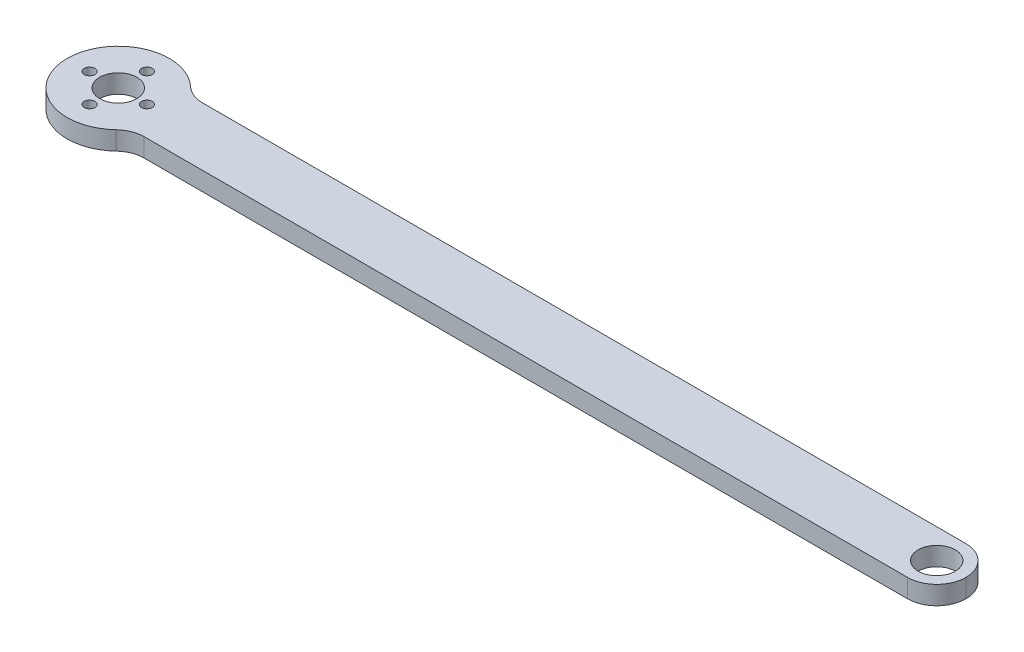
SolidWorks part; units mm, degrees
material "ABS"
ref_plane "Front Plane" through (0, 0, 0) normal (0, 0, 1) x (1, 0, 0)
ref_plane "Top Plane" through (0, 0, 0) normal (0, 1, 0) x (1, 0, 0)
ref_plane "Right Plane" through (0, 0, 0) normal (1, 0, 0) x (0, 0, -1)
sketch "Sketch1" plane through (0, 0, 0) normal (0, 1, 0) x (1, 0, 0)
  line L1 (-150, 10) -> (150, 10)
  line L2 (-150, 10) -> (-150, -10)
  line L3 (-150, -10) -> (150, -10)
  line L4 (150, 10) -> (150, -10)
  point P4 (0, -10)
  point P5 (0, 10)
  point P9 (150, 0)
  dimension "D1" = 300
  dimension "D2" = 20
extrude "Boss-Extrude1" add sketch "Sketch1" along normal blind 6.35
sketch "Sketch2" plane through (0, 0, 0) normal (0, -1, 0) x (-1, 0, 0)
  line L0 (-3.4925, 0) -> (3.4925, 0) construction
  line L1 (150, 10) -> (150, -10) construction
  circle A0 centre (140, 0) radius 6.35
  dimension "D1" = 12.7
  dimension "D2" = 10
extrude "Cut-Extrude1" cut sketch "Sketch2" against normal up to surface (6.35 mm away) up to face at (0, 6.35, 0)
mirror "Mirror1" about plane through (0, 0, 0) normal (1, 0, 0) of "Cut-Extrude1"
fillet "Congé1" radius 10 4 edges at (-150, 3.175, -10) (-150, 3.175, 10) (150, 3.175, -10) (150, 3.175, 10)
sketch "Sketch3" plane through (0, 6.35, 0) normal (0, 1, 0) x (1, 0, 0)
  circle A0 centre (-140, 0) radius 17.5
  circle A3 centre (-140, 0) radius 6.35 construction
  circle A4 centre (-140, 0) radius 6.35
  dimension "D2" = 35
extrude "Boss-Extrude2" add sketch "Sketch3" against normal up to surface (6.35 mm away) up to face at (140, 0, -6.35)
fillet "Fillet1" radius 10 2 edges at (-125.6386, 3.175, -10) (-125.6386, 3.175, 10)
sketch "Sketch5" plane through (0, 6.35, 0) normal (0, 1, 0) x (1, 0, 0)
  circle A0 centre (-130.221, 0) radius 1.83
  circle A1 centre (-140, -9.779) radius 1.83
  circle A2 centre (-149.779, 0) radius 1.83
  circle A3 centre (-140, 9.779) radius 1.83
  point P12 (-140, 0)
  point P13 (-140, -9.779)
  dimension "D1" = 3.66
  dimension "D2" = 4
extrude "Cut-Extrude2" cut sketch "Sketch5" against normal blind 10
